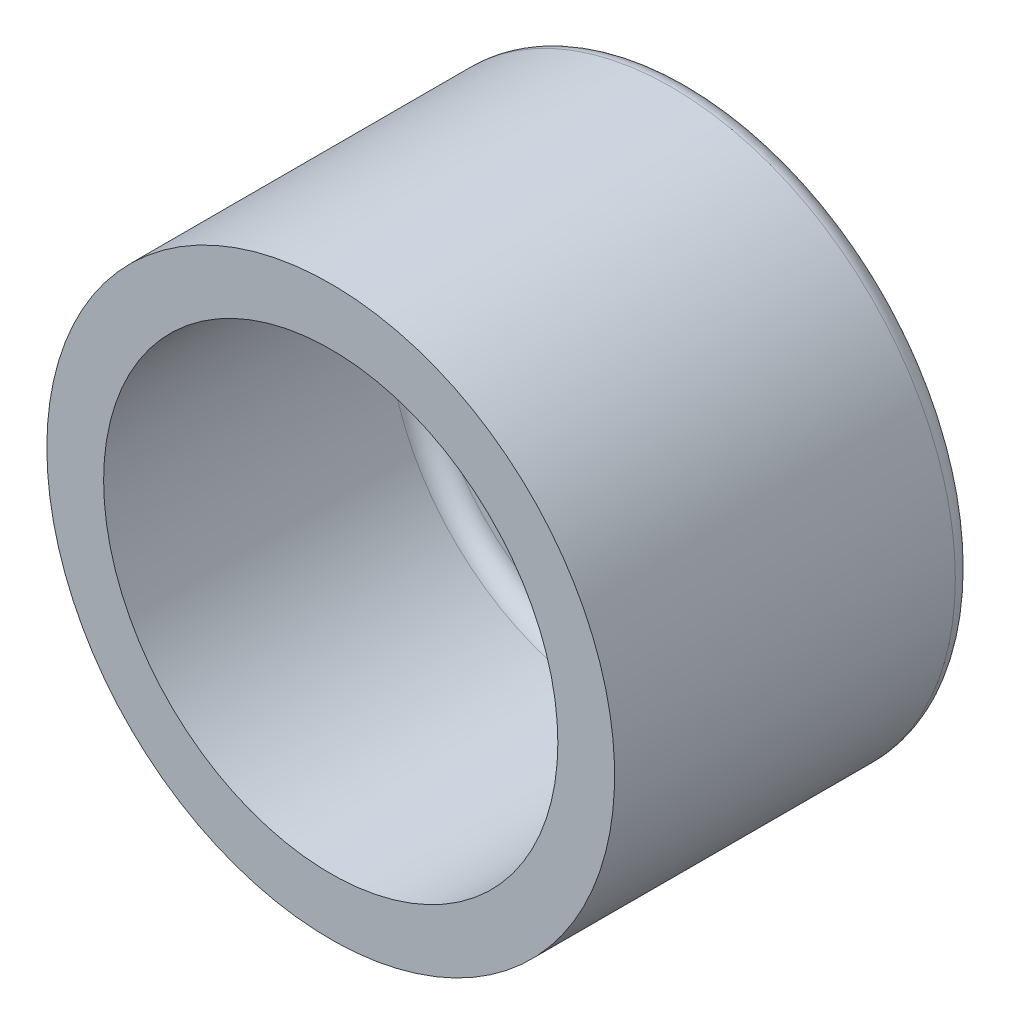
SolidWorks part; units mm, degrees
ref_plane "Front Plane" through (0, 0, 0) normal (0, 0, 1) x (1, 0, 0)
ref_plane "Top Plane" through (0, 0, 0) normal (0, 1, 0) x (1, 0, 0)
ref_plane "Right Plane" through (0, 0, 0) normal (1, 0, 0) x (0, 0, -1)
sketch "Sketch1" plane through (0, 0, 0) normal (0, 1, 0) x (1, 0, 0)
  line L0 (0, 0) -> (0, -8.1492) construction
  line L1 (0, 0) -> (6, 0)
  line L2 (0, 0) -> (0, 1.5)
  line L3 (0, 1.5) -> (7.5, 1.5)
  line L6 (7.5, 1.5) -> (7.5, -8)
  line L7 (7.5, -8) -> (6, -8)
  line L8 (6, 0) -> (6, -8)
  dimension "D1" = 6
  dimension "D2" = 1.5
  dimension "D3" = 8
revolve "Revolve1" add sketch "Sketch1" angle 360 about L0
fillet "Fillet1" radius 0.5 2 edges at (-7.5, 0, -1.5) (-6, 0, 0)
